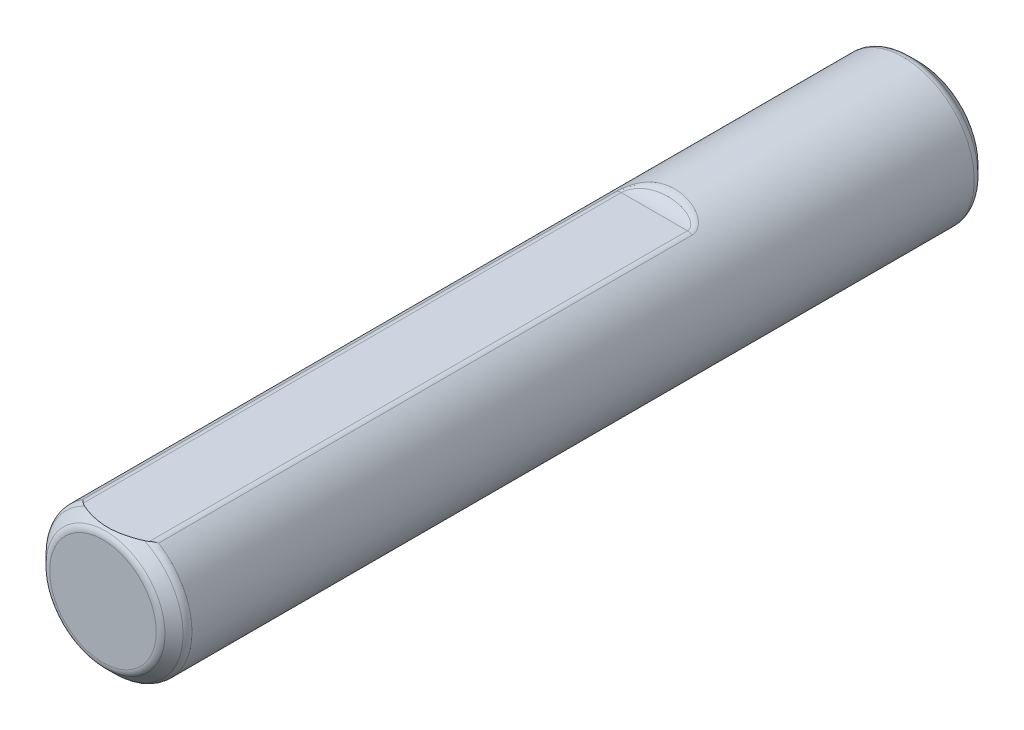
SolidWorks part; units mm, degrees
ref_plane "Front" through (0, 0, 0) normal (0, 0, 1) x (1, 0, 0)
ref_plane "Top" through (0, 0, 0) normal (0, 1, 0) x (1, 0, 0)
ref_plane "Right" through (0, 0, 0) normal (1, 0, 0) x (0, 0, -1)
sketch "Sketch1" plane through (0, 0, 0) normal (0, 0, 1) x (1, 0, 0)
  circle A0 centre (0, 0) radius 3.175
  dimension "D1" = 6.35
extrude "Extrude1" add sketch "Sketch1" along normal mid plane 36.5125
chamfer "Chamfer1" distance 0.635 angle 45 2 edges at (3.175, 0, -18.2562) (3.175, 0, 18.2562)
ref_plane "Plane1" through (0, 0, -7.1438) normal (0, 0, 1) x (1, 0, 0)
sketch "Sketch13" plane through (0, 0, -7.1438) normal (0, 0, 1) x (1, 0, 0)
  line L3 (-1.5875, 2.7496) -> (1.5875, 2.7496)
  circle A0 centre (0, 0) radius 3.175 construction
  arc A1 (1.5875, 2.7496) -> (-1.5875, 2.7496) centre (0, 0) ccw
  dimension "D1" = 3.175
extrude "Extrude7" cut sketch "Sketch13" along normal through all
fillet "Fillet1" radius 0.7937 1 edges at (0, 2.7496, -7.1438)
fillet "Fillet3" radius 0.3969 7 edges at (1.5875, 2.7496, 5.6356) (0, 3.175, -7.0531) (2.54, 0, -18.2562) (3.175, 0, -17.6212) (2.54, 0, 18.2562) (0, -3.175, 17.6212) (-1.5875, 2.7496, 5.6356)
equation "\"D1@Chamfer1\" = \"D1@Sketch1\" * .1"
equation "\"D1@Sketch13\" = \"D1@Sketch1\" * .5"
